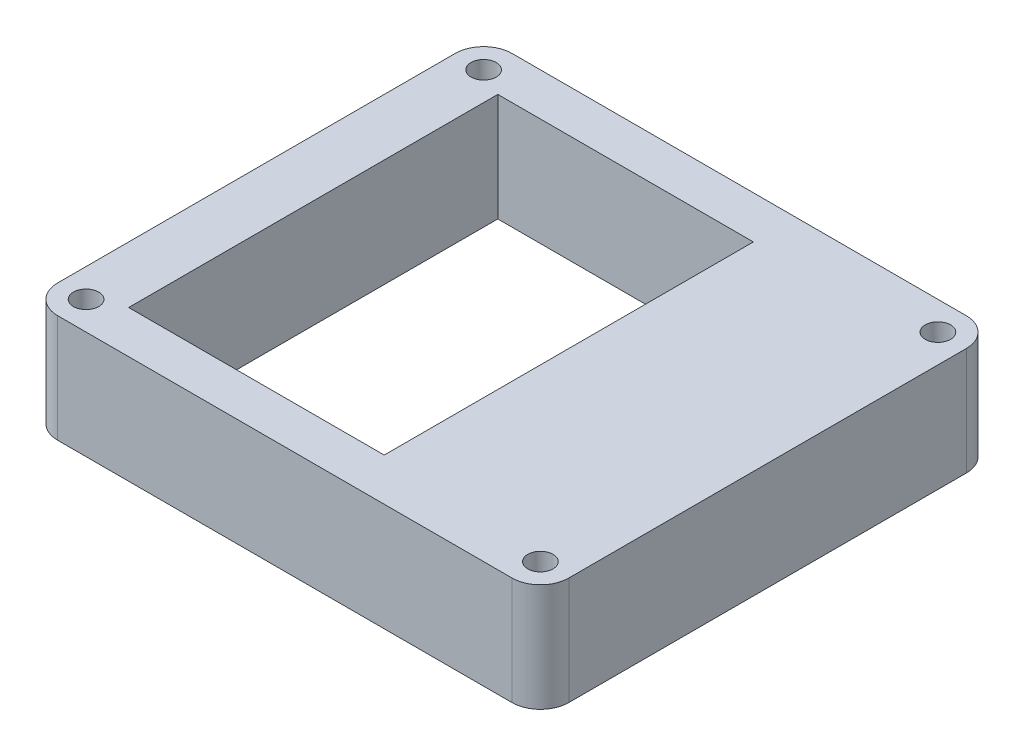
SolidWorks part; units mm, degrees
ref_plane "Front Plane" through (0, 0, 0) normal (0, 0, 1) x (1, 0, 0)
ref_plane "Top Plane" through (0, 0, 0) normal (0, 1, 0) x (1, 0, 0)
ref_plane "Right Plane" through (0, 0, 0) normal (1, 0, 0) x (0, 0, -1)
sketch "Sketch1" plane through (0, 0, 0) normal (0, 1, 0) x (1, 0, 0)
  line L1 (-22.86, 20.32) -> (22.86, 20.32)
  line L2 (-22.86, 20.32) -> (-22.86, -20.32)
  line L3 (-22.86, -20.32) -> (22.86, -20.32)
  line L4 (22.86, 20.32) -> (22.86, -20.32)
  line L5 (-22.86, 20.32) -> (22.86, -20.32) construction
  line L6 (-22.86, -20.32) -> (22.86, 20.32) construction
  point P0 (0, 0)
  dimension "D1" = 40.64
  dimension "D2" = 45.72
extrude "Body" add sketch "Sketch1" along normal mid plane 9.652
fillet "Fillet1" radius 2.54 4 edges at (22.86, 0, -20.32) (-22.86, 0, -20.32) (22.86, 0, 20.32) (-22.86, 0, 20.32)
hole_wizard "#4-40 Tapped Hole1" positions "Sketch2" profile "Sketch3" tap size "#4-40" standard "ANSI Inch" end condition through all
sketch "Sketch2" plane through (0, 4.826, 0) normal (0, 1, 0) x (1, 0, 0)
  line L1 (-20.32, -17.78) -> (20.32, -17.78)
  line L2 (-20.32, -17.78) -> (-20.32, 17.78)
  line L3 (-20.32, 17.78) -> (20.32, 17.78)
  line L4 (20.32, -17.78) -> (20.32, 17.78)
  line L5 (-20.32, -17.78) -> (20.32, 17.78) construction
  line L6 (-20.32, 17.78) -> (20.32, -17.78) construction
  point P2 (20.32, 17.78)
  point P63 (-20.32, -17.78)
  point P64 (-20.32, 17.78)
  point P65 (20.32, -17.78)
  dimension "D1" = 35.56
  dimension "D2" = 40.64
sketch "Sketch3" plane through (20.32, 4.826, -17.78) normal (1, 0, 0) x (0, 0, 1)
  line L0 (0, 0) -> (0, 9.652)
  line L1 (0, 9.652) -> (1.1303, 9.652)
  line L2 (1.1303, 9.652) -> (1.1303, 0)
  line L5 (1.1303, 0) -> (0, 0)
  line L11 (0, -6.35) -> (0, 107.95) construction
  dimension "Thru Tap Drill Dia." = 2.2606
  dimension "Thru Tap Drill Depth" = 9.652
cosmetic thread "Hole Thread1" parameters "D2"=2.8448
cosmetic thread "Hole Thread2" parameters "D2"=2.8448
cosmetic thread "Hole Thread3" parameters "D2"=2.8448
cosmetic thread "Hole Thread4" parameters "D2"=2.8448
sketch "Sketch4" plane through (0, 4.826, 0) normal (0, 1, 0) x (1, 0, 0)
  line L0 (-22.86, 17.78) -> (-22.86, -17.78) construction
  line L1 (5.08, 16.51) -> (-17.78, 16.51)
  line L2 (5.08, 16.51) -> (5.08, -16.51)
  line L3 (5.08, -16.51) -> (-17.78, -16.51)
  line L4 (-17.78, 16.51) -> (-17.78, -16.51)
  line L5 (5.08, 16.51) -> (-17.78, -16.51) construction
  line L6 (5.08, -16.51) -> (-17.78, 16.51) construction
  line L7 (-6.35, 0) -> (0, 0) construction
  point P0 (-6.35, 0)
  point P10 (-3.1218, 14.2435)
  dimension "D1" = 5.08
  dimension "D2" = 33.02
  dimension "D3" = 22.86
extrude "Cut-Extrude1" cut sketch "Sketch4" against normal through all
